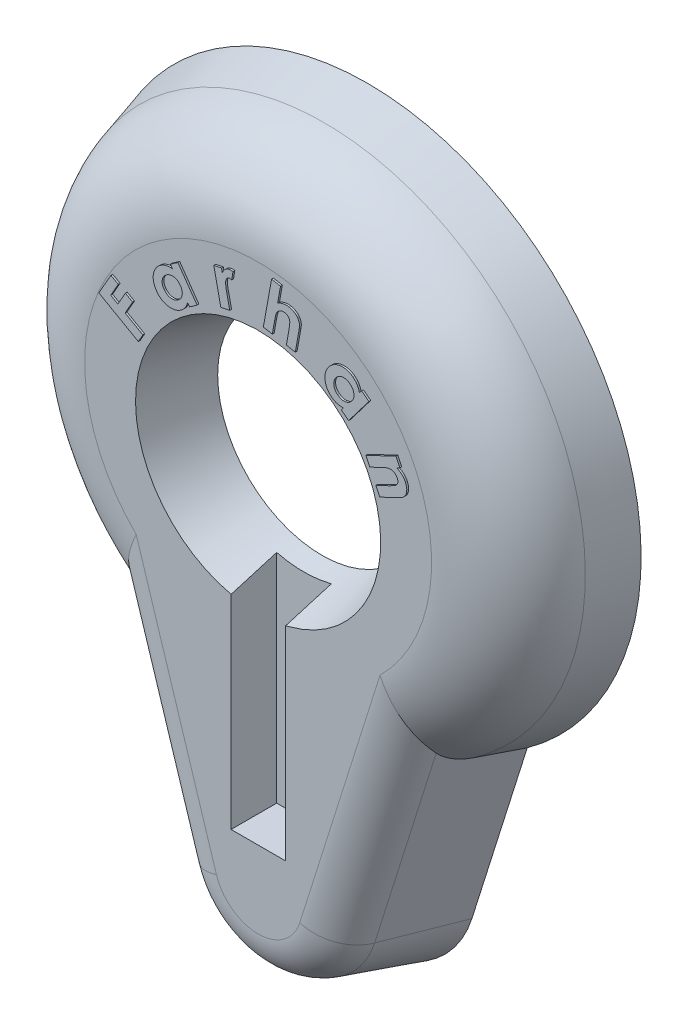
SolidWorks part; units mm, degrees
ref_plane "Front Plane" through (0, 0, 0) normal (0, 0, 1) x (1, 0, 0)
ref_plane "Top Plane" through (0, 0, 0) normal (0, 1, 0) x (1, 0, 0)
ref_plane "Right Plane" through (0, 0, 0) normal (1, 0, 0) x (0, 0, -1)
sketch "Sketch1" plane through (0, 0, 0) normal (0, 0, 1) x (1, 0, 0)
  line L0 (0, 49.6522) -> (0, 0) construction
  line L1 (0, 0) -> (-59.4079, 0) construction
  line L2 (-22.2438, 19.8674) -> (-14.5346, -4.5828)
  line L3 (22.2438, 19.8674) -> (14.5346, -4.5828)
  arc A0 (-22.2438, 19.8674) -> (22.2438, 19.8674) centre (0, 50.8) cw
  arc A1 (-14.5346, -4.5828) -> (14.5346, -4.5828) centre (0, 0) ccw
  circle A2 centre (0, 49.6522) radius 12.7
  dimension "D2" = 38.1
  dimension "D3" = 15.24
  dimension "D5" = 25.4
  dimension "D1" = 35
  dimension "D4" = 50.8
extrude "Boss-Extrude1" add sketch "Sketch1" along normal blind 15.24 draft 16
sketch "Sketch3" plane through (0, 0, 0) normal (0, 0, -1) x (-1, 0, 0)
  line L4 (-20.0801, 21.4521) -> (-12.1122, -3.819)
  line L5 (12.1122, -3.819) -> (20.0801, 21.4521)
  line L6 (-20.0801, 21.4521) -> (-12.1122, -3.819)
  line L7 (12.1122, -3.819) -> (20.0801, 21.4521)
  arc A4 (20.0801, 21.4521) -> (-20.0801, 21.4521) centre (0, 50.8) ccw
  arc A5 (-12.1122, -3.819) -> (12.1122, -3.819) centre (0, 0) ccw
  arc A6 (20.0801, 21.4521) -> (-20.0801, 21.4521) centre (0, 50.8) ccw
  arc A7 (-12.1122, -3.819) -> (12.1122, -3.819) centre (0, 0) ccw
  dimension "D1" = 2.54
extrude "Cut-Extrude2" cut sketch "Sketch3" against normal blind 6.35 draft 16
sketch "Sketch4" plane through (0, 0, 15.24) normal (0, 0, 1) x (1, 0, 0)
  line L1 (-3.761, 35.6269) -> (3.8488, 35.6269)
  line L2 (-3.761, 35.6269) -> (-3.761, 4.6389)
  line L3 (-3.761, 4.6389) -> (3.8488, 4.6389)
  line L4 (3.8488, 35.6269) -> (3.8488, 4.6389)
  circle A0 centre (0, 49.6522) radius 14.5208 construction
  dimension "D1" = 30.988
extrude "Cut-Extrude3" cut sketch "Sketch4" against normal blind 6.35
fillet "Fillet2" radius 6.35 3 edges at (-14.4473, 9.6728, 15.24) (14.4473, 9.6728, 15.24) (0, -10.87, 15.24)
fillet "Fillet3" radius 12.7 1 edges at (0, 84.53, 15.24)
sketch "Sketch5" plane through (0, 0, 15.24) normal (0, 0, 1) x (1, 0, 0)
  arc A0 (-16.825, 56.5779) -> (16.8493, 56.5184) centre (0, 49.6522) cw construction
  text T0 "Farhan" font "Century Gothic" height in points 24
extrude "Boss-Extrude2" add sketch "Sketch5" along normal blind 0.254
